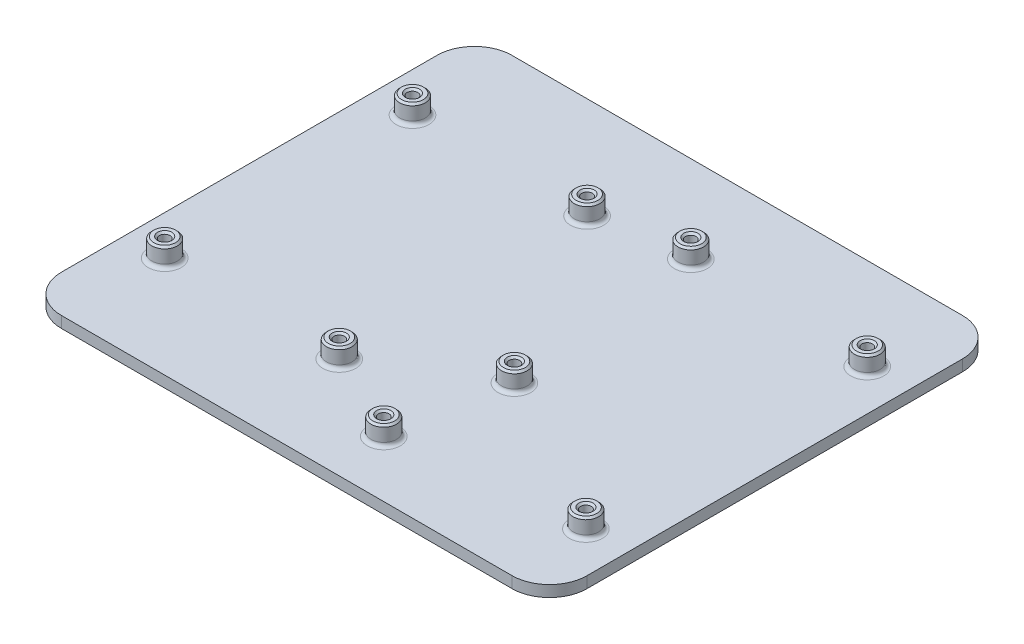
SolidWorks part; units mm, degrees
ref_plane "Front Plane" through (0, 0, 0) normal (0, 0, 1) x (1, 0, 0)
ref_plane "Top Plane" through (0, 0, 0) normal (0, 1, 0) x (1, 0, 0)
ref_plane "Right Plane" through (0, 0, 0) normal (1, 0, 0) x (0, 0, -1)
sketch "Sketch1" plane through (0, 0, 0) normal (0, 1, 0) x (1, 0, 0)
  line L0 (0, 87.1935) -> (0, -87.1935) construction
  line L5 (-36.2561, 38) -> (-36.2561, -38) construction
  line L7 (61.5961, -50.8) -> (8.2561, -50.8) construction
  line L8 (61.5961, -50.8) -> (61.5961, 50.8) construction
  line L9 (61.5961, 50.8) -> (8.2561, 50.8) construction
  line L10 (8.2561, -50.8) -> (8.2561, 50.8) construction
  line L11 (-101.4876, 0) -> (101.4876, 0) construction
  line L12 (-60, 60) -> (60, 60)
  line L13 (-64.2561, 38) -> (-8.2561, 38) construction
  line L14 (-64.2561, 38) -> (-64.2561, -38) construction
  line L15 (-64.2561, -38) -> (-8.2561, -38) construction
  line L16 (-8.2561, 38) -> (-8.2561, -38) construction
  line L17 (-70, 50) -> (-70, -50)
  line L18 (-60, -60) -> (60, -60)
  line L19 (70, 50) -> (70, -50)
  line L20 (-70, 60) -> (70, -60) construction
  line L21 (-70, -60) -> (70, 60) construction
  circle A0 centre (10.7961, 36.83) radius 1.4
  circle A1 centre (59.0561, 35.56) radius 1.4
  circle A2 centre (59.0561, -39.37) radius 1.4
  circle A3 centre (10.7961, -44.95) radius 1.4
  circle A4 centre (15.8761, -15.24) radius 1.4
  circle A5 centre (-59.5061, 33) radius 1.4
  circle A6 centre (-13.0061, 33) radius 1.4
  circle A7 centre (-13.0061, -33) radius 1.4
  circle A8 centre (-59.5061, -33) radius 1.4
  circle A9 centre (-59.5061, 33) radius 3.4
  circle A10 centre (-13.0061, 33) radius 3.4
  circle A11 centre (-13.0061, -33) radius 3.4
  circle A12 centre (-59.5061, -33) radius 3.4
  circle A13 centre (10.7961, -44.95) radius 3.4
  circle A14 centre (59.0561, -39.37) radius 3.4
  circle A15 centre (15.8761, -15.24) radius 3.4
  circle A16 centre (10.7961, 36.83) radius 3.4
  circle A17 centre (59.0561, 35.56) radius 3.4
  arc A18 (-60, -60) -> (-70, -50) centre (-60, -50) cw
  arc A19 (60, -60) -> (70, -50) centre (60, -50) ccw
  arc A20 (60, 60) -> (70, 50) centre (60, 50) cw
  arc A21 (-70, 50) -> (-60, 60) centre (-60, 50) cw
  point P0 (0, 0)
  point P13 (0, 0)
  point P16 (0, 0)
  point P40 (0, 0)
  dimension "D5" = 13.97
  dimension "D6" = 2.54
  dimension "D7" = 90.17
  dimension "D8" = 50.8
  dimension "D9" = 50.8
  dimension "D10" = 15.24
  dimension "D11" = 95.75
  dimension "D12" = 2.54
  dimension "D13" = 2.8
  dimension "D14" = 66.04
  dimension "D15" = 7.62
  dimension "D2" = 2.8
  dimension "D18" = 66
  dimension "D19" = 46.5
  dimension "D20" = 38
  dimension "D24" = 10
  dimension "D3" = 101.6
  dimension "D4" = 53.34
  dimension "D16" = 56
  dimension "D17" = 76
  dimension "D21" = 140
  dimension "D22" = 120
  dimension "D23" = 2
extrude "Boss-Extrude1" add sketch "Sketch1" against normal blind 3 contours L19 L12 L17 L18 A17 A16 A15 A14 A13 A12 A11 A10 A9 | A10 A6 | A6 | A9 A5 | A5 | A12 A8 | A8 | A11 A7 | A7 | A13 A3 | A3 | A15 A4 | A4 | A14 A2 | A2 | A0 | A16 A0 | A1 | A17 A1 region at (-0.0234, 0, -0.0602) region at (10.7961, 0, -36.83) region at (59.0561, 0, -35.56) region at (59.0561, 0, 39.37) region at (10.7961, 0, 44.95) region at (15.8761, 0, 15.24) region at (-59.5061, 0, -33) region at (-13.0061, 0, -33) region at (-13.0061, 0, 33) region at (-59.5061, 0, 33) region at (-62.8099, 0, -33) region at (-16.3099, 0, -33) region at (-16.3099, 0, 33) region at (-62.8099, 0, 33) region at (7.4922, 0, 44.95) region at (55.7522, 0, 39.37) region at (12.5722, 0, 15.24) region at (7.4922, 0, -36.83) region at (55.7522, 0, -35.56)
extrude "Boss-Extrude2" add sketch "Sketch1<5>" along normal blind 5 contours A12 A8 | A11 A7 | A13 A3 | A15 A4 | A14 A2 | A17 A1 | A16 A0 | A10 A6 | A9 A5 region at (-62.8099, 0, -33) region at (-16.3099, 0, -33) region at (-16.3099, 0, 33) region at (-62.8099, 0, 33) region at (7.4922, 0, 44.95) region at (55.7522, 0, 39.37) region at (12.5722, 0, 15.24) region at (7.4922, 0, -36.83) region at (55.7522, 0, -35.56)
sketch "Sketch1<5>" plane through (0, 0, 0) normal (0, 1, 0) x (1, 0, 0) same geometry as "Sketch1"
chamfer "Chamfer1" distance 0.5 angle 45 18 edges at (-59.5061, 5, 36.4) (-59.5061, 5, 34.4) (-13.0061, 5, 36.4) (-13.0061, 5, 34.4) (15.8761, 5, 18.64) (15.8761, 5, 16.64) (10.7961, 5, 48.35) (10.7961, 5, 46.35) (59.0561, 5, 42.77) (59.0561, 5, 40.77) (59.0561, 5, -32.16) (59.0561, 5, -34.16) (10.7961, 5, -33.43) (10.7961, 5, -35.43) (-13.0061, 5, -29.6) (-13.0061, 5, -31.6) (-59.5061, 5, -29.6) (-59.5061, 5, -31.6)
fillet "Fillet1" radius 1 9 edges at (-59.5061, 0, -29.6) (-13.0061, 0, -29.6) (10.7961, 0, -33.43) (59.0561, 0, -32.16) (59.0561, 0, 42.77) (15.8761, 0, 18.64) (10.7961, 0, 48.35) (-13.0061, 0, 36.4) (-59.5061, 0, 36.4)
